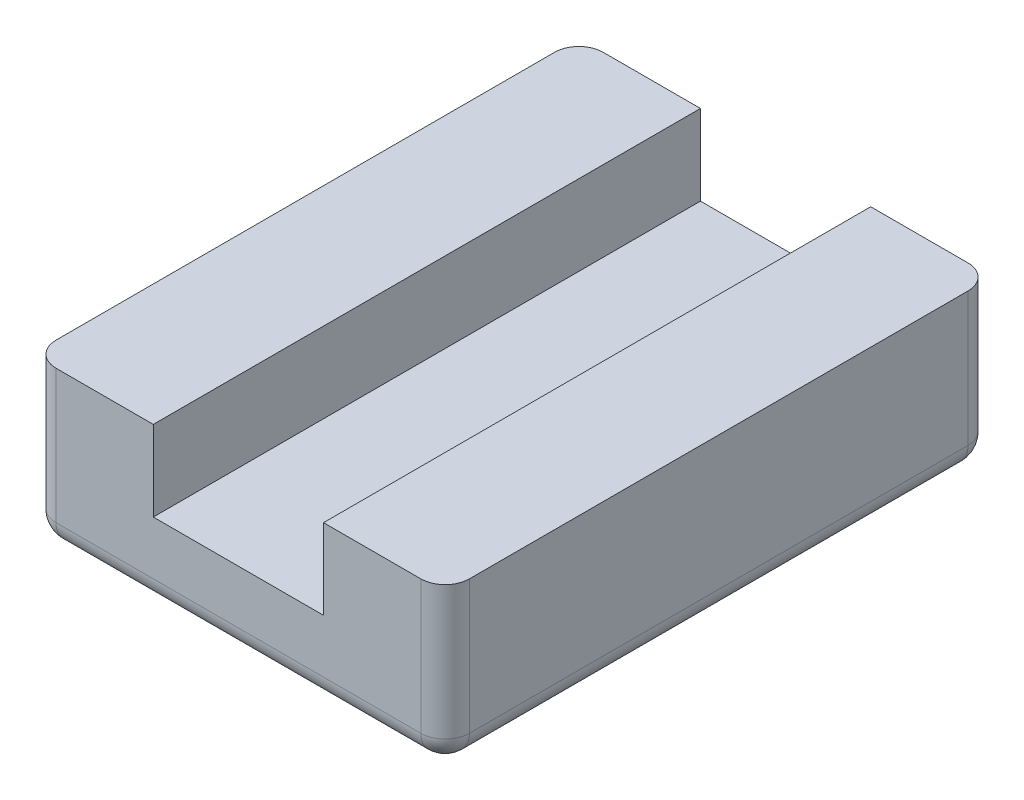
SolidWorks part; units mm, degrees
ref_plane "前视基准面" through (0, 0, 0) normal (0, 0, 1) x (1, 0, 0)
ref_plane "上视基准面" through (0, 0, 0) normal (0, 1, 0) x (1, 0, 0)
ref_plane "右视基准面" through (0, 0, 0) normal (1, 0, 0) x (0, 0, -1)
sketch "草图1" plane through (0, 0, 0) normal (0, 0, 1) x (1, 0, 0)
  line L1 (-8.5, -3.25) -> (8.5, -3.25)
  line L2 (-8.5, -3.25) -> (-8.5, 3.25)
  line L3 (-8.5, 3.25) -> (8.5, 3.25)
  line L4 (8.5, -3.25) -> (8.5, 3.25)
  line L5 (-8.5, -3.25) -> (8.5, 3.25) construction
  line L6 (-8.5, 3.25) -> (8.5, -3.25) construction
  line L7 (-3.5, 3.25) -> (3.5, 3.25)
  line L8 (-3.5, 3.25) -> (-3.5, -0.05)
  line L9 (-3.5, -0.05) -> (3.5, -0.05)
  line L10 (3.5, 3.25) -> (3.5, -0.05)
  point P0 (0, 0)
  point P10 (0, -0.05)
  dimension "D1" = 6.5
  dimension "D2" = 17
  dimension "D3" = 7
  dimension "D4" = 3.3
extrude "凸台-拉伸1" add sketch "草图1" against normal blind 22.5 contours L3 L10 L9 L8 L2 L1 L4 region at (0, -0.4229, 0)
sketch "草图2" plane through (0, -3.25, 0) normal (0, -1, 0) x (1, 0, 0)
  line L0 (-8.5, -22.5) -> (-8.5, 0) construction
  line L1 (-6, -7.25) -> (6, -7.25)
  line L2 (-6, -7.25) -> (-6, -15.25)
  line L3 (-6, -15.25) -> (6, -15.25)
  line L4 (6, -7.25) -> (6, -15.25)
  circle A0 centre (-6, -7.25) radius 1
  circle A1 centre (6, -7.25) radius 1
  circle A2 centre (6, -15.25) radius 1
  circle A3 centre (-6, -15.25) radius 1
  point P4 (0, -7.25)
  point P6 (-6, -11.25)
  point P9 (-8.5, -11.25)
  dimension "D3" = 2
  dimension "D4" = 2
  dimension "D5" = 2
  dimension "D6" = 2
  dimension "D1" = 8
  dimension "D2" = 12
extrude "切除-拉伸1" cut sketch "草图2" against normal blind 2.5 contours L1 A0 L2 | L2 A0 L1 | L4 A1 L1 | L1 A1 L4 | L3 A2 L4 | L4 A2 L3 | L2 A3 L3 | L3 A3 L2 region at (-6.1415, -3.25, -7.1085) region at (-5.5756, -3.25, -7.6744) region at (6.1415, -3.25, -7.1085) region at (5.5756, -3.25, -7.6744) region at (-5.5756, -3.25, -14.8256) region at (-6.1415, -3.25, -15.3915) region at (6.1415, -3.25, -15.3915) region at (5.5756, -3.25, -14.8256)
fillet "圆角1" radius 1 4 edges at (0, -3.25, -22.5) (8.5, -3.25, -11.25) (0, -3.25, 0) (-8.5, -3.25, -11.25)
fillet "圆角2" radius 1 8 edges at (8.2071, -2.9571, -0.2929) (8.2071, -2.9571, -22.2071) (-8.2071, -2.9571, -22.2071) (-8.2071, -2.9571, -0.2929) (8.5, 0.5, 0) (8.5, 0.5, -22.5) (-8.5, 0.5, -22.5) (-8.5, 0.5, 0)
